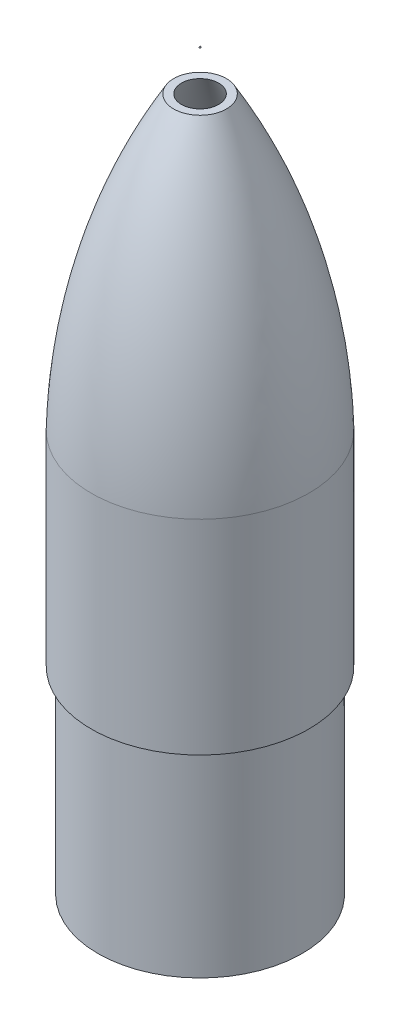
SolidWorks part; units mm, degrees
material "A-Glass Fiber"
ref_plane "Front Plane" through (0, 0, 0) normal (0, 0, 1) x (1, 0, 0)
ref_plane "Top Plane" through (0, 0, 0) normal (0, 1, 0) x (1, 0, 0)
ref_plane "Right Plane" through (0, 0, 0) normal (1, 0, 0) x (0, 0, -1)
sketch "Sketch1" plane through (0, 0, 0) normal (0, 0, 1) x (1, 0, 0)
  line L0 (81.2, -0.8712) -> (81.2, 151.5288)
  line L3 (76.2, -0.8712) -> (76.2, 151.4686)
  line L6 (0, -198.8179) -> (0, -350.074)
  line L7 (0, 391.1408) -> (0, 400)
  line L8 (0, 0) -> (0, 391.1408) construction
  line L9 (81.2, -0.8712) -> (76.2, -0.8712)
  spline S0 degree 4 poles (-15.6057, 421.1065) (-15.2639, 420.6711) (-14.5817, 419.7992) (-13.562, 418.4872) (-12.2126, 416.7336) (-10.8751, 414.9774) (-9.5572, 413.2301) (-8.244, 411.4704) (-6.9642, 409.7399) (-5.6553, 407.9493) (-4.4289, 406.2592) (-3.0638, 404.3513) (-2.0014, 402.8605) (-0.4346, 400.6256) (0.2786, 399.6012) (1.5658, 397.7374) (2.5679, 396.2716) (3.5695, 394.7941) (4.5833, 393.2862) (5.5835, 391.7855) (6.5792, 390.2787) (7.5743, 388.7596) (8.5687, 387.2282) (16.8048, 374.4321) (28.9156, 353.6941) (43.4689, 324.2779) (58.9536, 283.7096) (70.3633, 243.7204) (76.4231, 210.9959) (79.2777, 185.7606) (80.3203, 171.0312) (80.5215, 167.8173) (80.6748, 165.0728) (80.7688, 163.2592) (80.8551, 161.4552) (80.9342, 159.6535) (81.0064, 157.8378) (81.0706, 156.0544) (81.1275, 154.2787) (81.1894, 152.013) (81.2188, 150.7624) (81.2744, 148.0224) (81.2973, 146.1866) (81.3223, 143.829) (81.3305, 141.7333) (81.3314, 139.5051) (81.3201, 137.3443) (81.2991, 135.1392) (81.2669, 132.9418) (81.224, 130.7253) (81.17, 128.5039) (81.1213, 126.836) (81.0852, 125.7248) (81.0662, 125.1693) knots 0 0 0 0 0 0.006969 0.013937 0.020906 0.027875 0.034717 0.04156 0.048403 0.055246 0.062088 0.068931 0.075774 0.082616 0.0883 0.093983 0.099666 0.10535 0.111033 0.116716 0.122399 0.128083 0.133891 0.1397 0.313954 0.430124 0.546294 0.685698 0.836718 0.848335 0.865761 0.871569 0.877253 0.882936 0.888619 0.894302 0.899986 0.905669 0.911352 0.917035 0.923907 0.930779 0.93765 0.944522 0.951393 0.958265 0.965136 0.972008 0.979006 0.986004 0.993002 1 1 1 1 1 construction
  spline S1 degree 4 poles (0, 400) (0.2151, 399.6907) (0.6473, 399.0674) (1.5658, 397.7374) (2.5679, 396.2716) (3.5695, 394.7941) (4.5833, 393.2862) (5.5835, 391.7855) (6.5792, 390.2787) (7.5743, 388.7596) (8.5687, 387.2282) (16.8048, 374.4321) (28.9156, 353.6941) (43.4689, 324.2779) (58.9536, 283.7096) (70.3633, 243.7204) (76.4231, 210.9959) (79.2777, 185.7606) (80.3203, 171.0312) (80.5215, 167.8173) (80.6748, 165.0728) (80.7688, 163.2592) (80.8551, 161.4552) (80.9342, 159.6535) (81.0064, 157.8378) (81.0706, 156.0544) (81.1275, 154.2787) (81.1716, 152.6638) (81.191, 151.9054) (81.2, 151.5288) knots 0.082616 0.082616 0.082616 0.082616 0.082616 0.0883 0.093983 0.099666 0.10535 0.111033 0.116716 0.122399 0.128083 0.133891 0.1397 0.313954 0.430124 0.546294 0.685698 0.836718 0.848335 0.865761 0.871569 0.877253 0.882936 0.888619 0.894302 0.899986 0.905669 0.911352 0.917035 0.917035 0.917035 0.917035 0.917035
  spline S2 degree 1 poles (-4.1046, 397.1448) (76.2, 151.4686) knots 0 0 1 1 construction
  spline S3 degree 3 poles (-4.1046, 397.1448) (-3.9331, 396.8983) (-3.6166, 396.4418) (-2.989, 395.5335) (-2.3524, 394.608) (-1.7694, 393.7556) (-1.2022, 392.9218) (-0.4422, 391.7993) (0.8967, 389.8077) (2.7782, 386.9665) (7.2414, 380.0924) (16.5651, 364.9882) (34.8525, 331.3819) (55.6166, 280.7096) (68.7916, 227.5567) (73.8849, 189.6374) (75.2829, 171.9424) (75.7417, 163.7592) (75.9016, 160.3555) (75.9976, 157.9574) (76.0474, 156.6021) (76.0822, 155.5937) (76.1152, 154.5665) (76.148, 153.4463) (76.1731, 152.5282) (76.1895, 151.8967) (76.1965, 151.6141) (76.2, 151.4686) knots 0.082616 0.082616 0.082616 0.082616 0.085875 0.089134 0.092392 0.095651 0.098909 0.102168 0.108685 0.121719 0.134753 0.18689 0.291164 0.499712 0.708259 0.812533 0.86467 0.877704 0.890739 0.897256 0.900514 0.903773 0.907031 0.91029 0.913549 0.915178 0.916807 0.916807 0.916807 0.916807 only from (0, 391.1408) to (76.2, 151.4686)
  dimension "D1" = 400
  dimension "D2" = 152.4
  dimension "D3" = 5
  dimension "D5" = 81.2
revolve "Revolve3" add sketch "Sketch1" angle 360 about L6 reverse direction yes
ref_plane "Plane1" through (0, 151.5288, 0) normal (0, 1, 0) x (1, 0, 0)
sketch "Sketch2" plane through (0, 151.5288, 0) normal (0, 1, 0) x (1, 0, 0)
  circle A3 centre (0, 0) radius 76.2 construction
  circle A4 centre (0, 0) radius 76.2
  circle A5 centre (0, 0) radius 74.2
  dimension "D1" = 2
extrude "Boss-Extrude1" add sketch "Sketch2" against normal blind 300
ref_plane "Plane2" through (0, 399.1288, 0) normal (0, -1, 0) x (-1, 0, 0)
sketch "Sketch3" plane through (0, 399.1288, 0) normal (0, -1, 0) x (-1, 0, 0)
  circle A0 centre (0, 0) radius 132.2448
extrude "Cut-Extrude1" cut sketch "Sketch3" along normal blind 30
